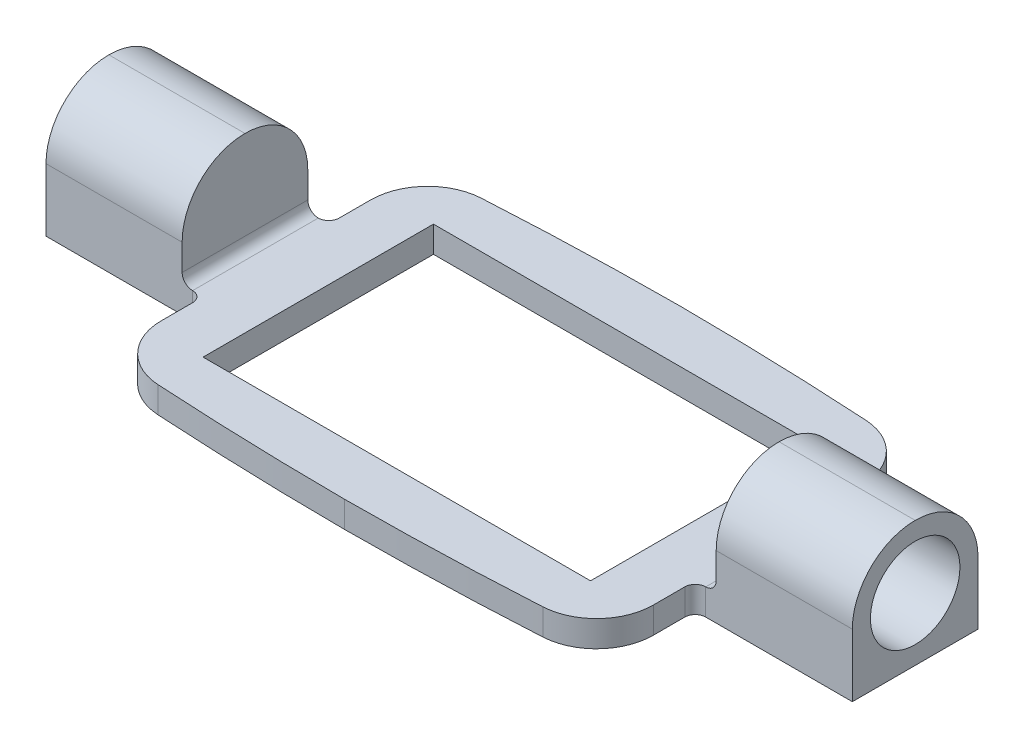
SolidWorks part; units mm, degrees
ref_plane "Front Plane" through (0, 0, 0) normal (0, 0, 1) x (1, 0, 0)
ref_plane "Top Plane" through (0, 0, 0) normal (0, 1, 0) x (1, 0, 0)
ref_plane "Right Plane" through (0, 0, 0) normal (1, 0, 0) x (0, 0, -1)
sketch "Sketch2" plane through (0, 0, 0) normal (0, 1, 0) x (1, 0, 0)
  line L0 (-46.99, 27.94) -> (-93.6881, -11.2443) construction
  line L1 (0, 0) -> (-93.98, 0)
  line L2 (0, 0) -> (0, 55.88)
  line L3 (0, 55.88) -> (-93.98, 55.88)
  line L4 (-93.98, 0) -> (-93.98, 55.88)
  line L5 (-46.99, 55.88) -> (-46.99, 27.94) construction
  line L6 (-46.99, 27.94) -> (-0.2919, -11.2443) construction
  line L7 (-46.99, 27.94) -> (-219.5694, 27.94) construction
  line L8 (-44.4992, -12.7) -> (-49.4808, -12.7)
  line L9 (-144.78, 12.7) -> (-106.68, 12.7)
  line L10 (-46.99, 27.94) -> (69.9568, 27.94) construction
  line L11 (-106.68, 2.54) -> (-106.68, 12.7)
  line L12 (-144.78, 12.7) -> (-144.78, 43.18)
  line L13 (12.7, 2.54) -> (12.7, 12.7)
  line L14 (12.7, 12.7) -> (50.8, 12.7)
  line L15 (50.8, 12.7) -> (50.8, 43.18)
  line L16 (12.7, 43.18) -> (50.8, 43.18)
  line L17 (12.7, 53.34) -> (12.7, 43.18)
  line L18 (-106.68, 53.34) -> (-106.68, 43.18)
  line L19 (-144.78, 43.18) -> (-106.68, 43.18)
  arc A0 (-44.4992, -12.7) -> (-93.6881, -11.2443) centre (-44.4992, 819.1044) cw
  arc A1 (-93.6881, -11.2443) -> (-106.68, 2.54) centre (-92.8715, 2.54) cw
  arc A2 (-49.4808, -12.7) -> (-0.2919, -11.2443) centre (-49.4808, 819.1044) ccw
  arc A3 (-0.2919, -11.2443) -> (12.7, 2.54) centre (-1.1085, 2.54) ccw
  arc A4 (-0.2919, 67.1243) -> (12.7, 53.34) centre (-1.1085, 53.34) cw
  arc A5 (-49.4808, 68.58) -> (-0.2919, 67.1243) centre (-49.4808, -763.2244) cw
  arc A6 (-44.4992, 68.58) -> (-93.6881, 67.1243) centre (-44.4992, -763.2244) ccw
  arc A7 (-93.6881, 67.1243) -> (-106.68, 53.34) centre (-92.8715, 53.34) ccw
  point P7 (0, 27.94)
  point P8 (-46.99, 55.88)
  point P25 (12.7, 27.94)
  point P29 (50.8, 27.94)
  point P34 (-106.68, 27.94)
  point P43 (-144.78, 27.94)
  dimension "D9" = 25.4
  dimension "D1" = 93.98
  dimension "D2" = 55.88
  dimension "D3" = 130
  dimension "D4" = 130
  dimension "D5" = 60.96
  dimension "D6" = 60.96
  dimension "D7" = 15.24
  dimension "D8" = 12.7
  dimension "D10" = 10.16
  dimension "D11" = 25.4
  dimension "D12" = 15.24
  dimension "D13" = 10.16
  dimension "D14" = 38.1
  dimension "D15" = 38.1
  dimension "D16" = 12.7
  dimension "D17" = 12.7
extrude "Boss-Extrude1" add sketch "Sketch2" along normal blind 6.35 contours A1 A0 A2 A3 L1 L4 L3 L2 region at (-70.2834, 0, 10.1813)
sketch "Sketch3" plane through (0, 6.35, 0) normal (0, 1, 0) x (1, 0, 0)
  line L0 (-46.99, 68.5763) -> (-46.99, -12.6963) construction
  line L1 (12.7, 12.7) -> (50.8, 12.7) construction
  line L2 (50.8, 43.18) -> (17.78, 43.18)
  line L3 (50.8, 43.18) -> (50.8, 12.7)
  line L4 (50.8, 12.7) -> (17.78, 12.7)
  line L5 (17.78, 43.18) -> (17.78, 12.7)
  line L6 (-144.78, 12.7) -> (-111.76, 12.7)
  line L7 (-111.76, 43.18) -> (-111.76, 12.7)
  line L8 (-144.78, 43.18) -> (-111.76, 43.18)
  line L9 (-144.78, 43.18) -> (-144.78, 12.7)
  dimension "D1" = 33.02
extrude "Boss-Extrude2" add sketch "Sketch3" along normal blind 24.13
fillet "Fillet1" radius 2.54 2 edges at (17.78, 6.35, -27.94) (-111.76, 6.35, -27.94)
sketch "Sketch4" plane through (50.8, 0, 0) normal (1, 0, 0) x (0, 0, -1)
  line L1 (12.7, 30.48) -> (12.7, 0) construction
  line L2 (12.7, 30.48) -> (43.18, 30.48) construction
  circle A0 centre (27.94, 15.24) radius 10.8585
  point P4 (12.7, 15.24)
  point P7 (27.94, 30.48)
  dimension "D1" = 21.717
extrude "Cut-Extrude1" cut sketch "Sketch4" against normal blind 25.4
sketch "Sketch5" plane through (-144.78, 0, 0) normal (-1, 0, 0) x (0, 0, 1)
  line L0 (-43.18, 30.48) -> (-43.18, 0) construction
  line L1 (-43.18, 30.48) -> (-12.7, 30.48) construction
  circle A0 centre (-27.94, 15.24) radius 10.8585
  point P5 (-43.18, 15.24)
  point P8 (-27.94, 30.48)
  dimension "D1" = 21.717
extrude "Cut-Extrude2" cut sketch "Sketch5" against normal blind 25.4
fillet "Fillet2" radius 2.54 4 edges at (12.7, 3.175, -43.18) (12.7, 3.175, -12.7) (-106.68, 3.175, -43.18) (-106.68, 3.175, -12.7)
fillet "Fillet3" radius 15.24 4 edges at (34.29, 30.48, -43.18) (34.29, 30.48, -12.7) (-128.27, 30.48, -43.18) (-128.27, 30.48, -12.7)
